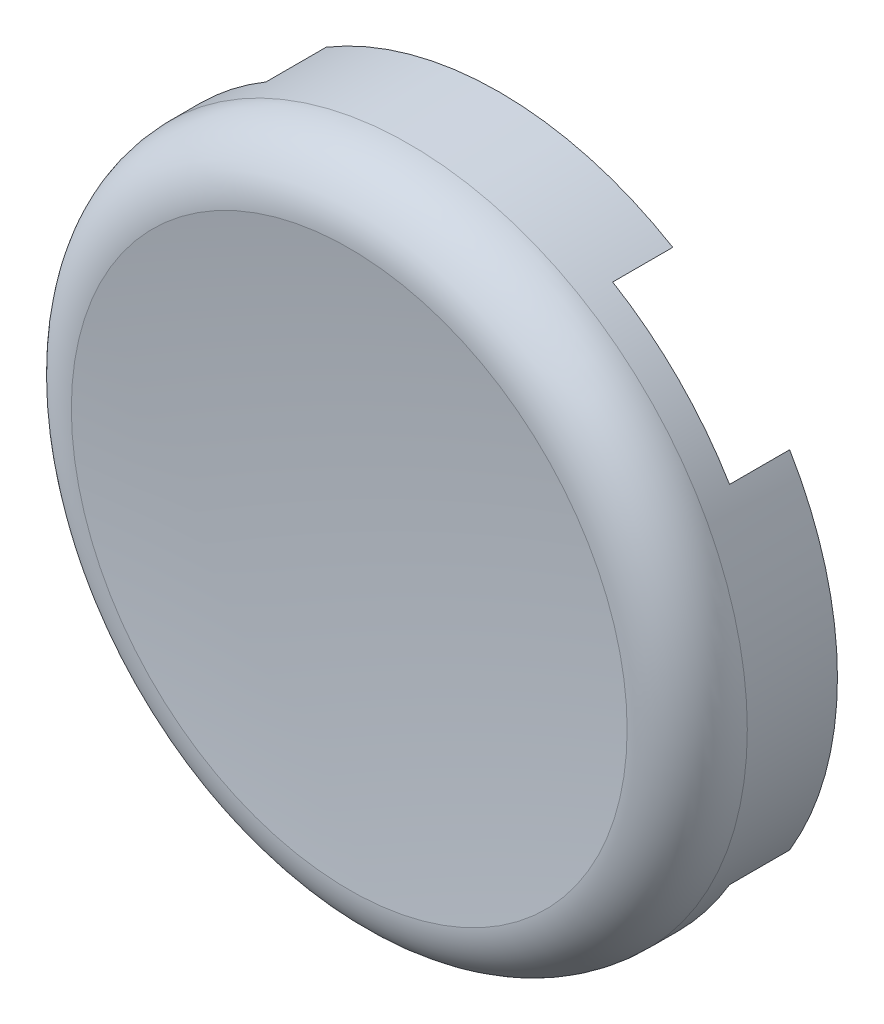
SolidWorks part; units mm, degrees
ref_plane "Front Plane" through (0, 0, 0) normal (0, 0, 1) x (1, 0, 0)
ref_plane "Top Plane" through (0, 0, 0) normal (0, 1, 0) x (1, 0, 0)
ref_plane "Right Plane" through (0, 0, 0) normal (1, 0, 0) x (0, 0, -1)
sketch "Sketch1" plane through (0, 0, 0) normal (0, 1, 0) x (1, 0, 0)
  line L1 (0, 0) -> (11.25, 0)
  line L2 (0, 0) -> (0, -5)
  line L3 (0, -5) -> (11.25, -5)
  line L4 (11.25, 0) -> (11.25, -5)
  line L5 (0, 0) -> (2.8, 0)
  line L6 (0, 0) -> (0, 1.2)
  line L7 (0, 1.2) -> (2.8, 1.2)
  line L8 (2.8, 0) -> (2.8, 1.2)
  line L9 (2.8, 0) -> (9.75, 0)
  line L10 (2.8, 0) -> (2.8, -3.6)
  line L11 (2.8, -3.6) -> (9.75, -3.6)
  line L12 (9.75, 0) -> (9.75, -3.6)
  line L13 (0, -5) -> (-11.25, -5)
  line L15 (2.8, -3.6) -> (9.75, -3.6)
  line L16 (2.8, -3.6) -> (2.8, -3.1)
  line L17 (2.8, -3.1) -> (9.75, -3.1)
  line L18 (9.75, -3.6) -> (9.75, -3.1)
  circle A0 centre (0, -90.3125) radius 85.8125
  point P11 (0, -4.5)
  point P14 (-9.25, -5)
  point P22 (9.25, -5)
  dimension "D1" = 11.25
  dimension "D2" = 6.2
  dimension "D3" = 2.8
  dimension "D4" = 5
  dimension "D5" = 1.4
  dimension "D6" = 1.5
  dimension "D7" = 0.5
  dimension "D8" = 11.25
  dimension "D9" = 2
  dimension "D11" = 0.5
  dimension "D10" = 2
revolve "Revolve1" add sketch "Sketch1" angle 360 about L2 region at (1.4, 0, -0.6) region at (1.4, 0, 0.1231) region at (6.275, 0, 3.35)
sketch "Sketch2" plane through (0, 0, 0) normal (0, 0, 1) x (1, 0, 0)
  line L0 (6.0104, 9.8995) -> (9.8995, 6.0104)
  line L1 (8.5589, 8.5589) -> (-8.5589, 8.5589)
  line L2 (8.5589, 8.5589) -> (8.5589, -8.5589)
  line L3 (8.5589, -8.5589) -> (-8.5589, -8.5589)
  line L4 (-8.5589, 8.5589) -> (-8.5589, -8.5589)
  line L5 (9.8995, 6.0104) -> (-6.0104, -9.8995)
  line L6 (-6.0104, -9.8995) -> (-9.8995, -6.0104)
  line L7 (-9.8995, -6.0104) -> (6.0104, 9.8995)
  line L8 (-6.0104, 9.8995) -> (9.8995, -6.0104)
  line L9 (9.8995, -6.0104) -> (6.0104, -9.8995)
  line L10 (6.0104, -9.8995) -> (-9.8995, 6.0104)
  line L11 (-9.8995, 6.0104) -> (-6.0104, 9.8995)
  circle A0 centre (0, 0) radius 9.75
  circle A1 centre (0, 0) radius 9.75 construction
  circle A3 centre (0, 0) radius 11.25 construction
  point P4 (0, 8.5589)
  point P6 (8.5589, 0)
  point P12 (8.5589, 4.6698)
  point P13 (4.6698, 8.5589)
  point P14 (-8.5589, 4.6698)
  point P15 (-8.5589, -4.6698)
  point P16 (-4.6698, 8.5589)
  point P17 (-4.6698, -8.5589)
  point P18 (4.6698, -8.5589)
  point P19 (8.5589, -4.6698)
  dimension "D1" = 5.5
extrude "Cut-Extrude2" cut sketch "Sketch2" along normal offset from surface (2 mm away) 2 contours A0 L2 L0 L1 | L7 L1 L0 | L5 L0 L2 | L9 L8 L2 | A0 L3 L9 L2 | L10 L9 L3 | L6 L5 L3 | A0 L4 L6 L3 | L7 L6 L4 | L11 L10 L4 | A0 L1 L11 L4 | L11 L1 L8 region at (6.0104, 9.0058, 0) region at (7.2866, 7.2866, 0) region at (9.0058, 6.0104, 0) region at (-7.2866, 7.2866, 0) region at (-6.0104, 9.0058, 0) region at (-9.0058, 6.0104, 0) region at (9.0058, -6.0104, 0) region at (7.2866, -7.2866, 0) region at (-7.2866, -7.2866, 0) region at (-9.0058, -6.0104, 0) region at (6.0104, -9.0058, 0) region at (-6.0104, -9.0058, 0) up to face at (-11.25, 0, 0)
sketch "Sketch3" plane through (0, 0, -1.2) normal (0, 0, -1) x (-1, 0, 0)
  line L1 (-2.05, 0.585) -> (2.05, 0.585)
  line L2 (-2.05, 0.585) -> (-2.05, -0.585)
  line L3 (-2.05, -0.585) -> (2.05, -0.585)
  line L4 (2.05, 0.585) -> (2.05, -0.585)
  line L5 (-0.585, 2.05) -> (0.585, 2.05)
  line L6 (-0.585, 2.05) -> (-0.585, -2.05)
  line L7 (-0.585, -2.05) -> (0.585, -2.05)
  line L8 (0.585, 2.05) -> (0.585, -2.05)
  point P8 (0.585, 0)
  point P10 (2.05, 0)
  point P11 (0, 2.05)
  point P12 (0, 0.585)
  dimension "D1" = 1.17
  dimension "D2" = 4.1
extrude "Cut-Extrude3" cut sketch "Sketch3" against normal up to surface (4.3 mm away) contours L8 L5 L6 L1 | L8 L1 L6 L3 | L8 L3 L6 L7 | L6 L1 L2 L3 | L1 L8 L3 L4 region at (1.3175, 0, -1.2) region at (0, 1.3175, -1.2) region at (0, 0, -1.2) region at (-1.3175, 0, -1.2) region at (0, -1.3175, -1.2) up to face at (-9.75, 0, 3.1)
fillet "Fillet1" radius 0.3 4 edges at (-0.585, -0.585, 0.95) (0.585, -0.585, 0.95) (-0.585, 0.585, 0.95) (0.585, 0.585, 0.95)
fillet "Fillet2" radius 1 1 edges at (-9.75, 0, 3.1)
fillet "Fillet3" radius 2 1 edges at (-11.25, 0, 5)
